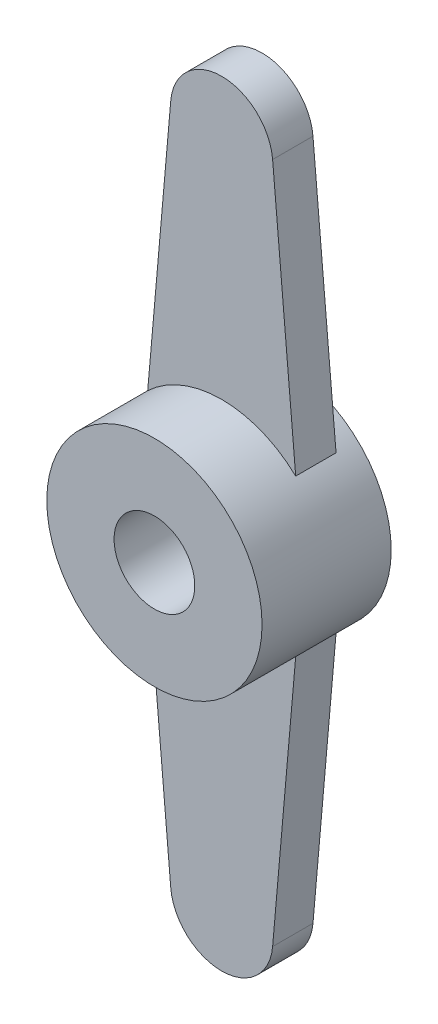
SolidWorks part; units mm, degrees
ref_plane "Front Plane" through (0, 0, 0) normal (0, 0, 1) x (1, 0, 0)
ref_plane "Top Plane" through (0, 0, 0) normal (0, 1, 0) x (1, 0, 0)
ref_plane "Right Plane" through (0, 0, 0) normal (1, 0, 0) x (0, 0, -1)
sketch "Sketch1" plane through (0, 0, 0) normal (0, 0, 1) x (1, 0, 0)
  line L0 (0, 0) -> (0, 15282.2833) construction
  line L1 (0, 0) -> (15282.2833, 0) construction
  line L2 (-1.8927, 12.6662) -> (-2.75, 2.9047)
  line L3 (1.8927, 12.6662) -> (2.75, 2.9047)
  line L4 (-2.75, -2.9047) -> (-1.8927, -12.6662)
  line L5 (2.75, -2.9047) -> (1.8927, -12.6662)
  line L6 (-2.75, -2.9047) -> (2.75, -2.9047) construction
  line L7 (2.75, 2.9047) -> (-2.75, 2.9047) construction
  line L8 (-2.75, 2.9047) -> (-2.75, -2.9047) construction
  line L9 (2.75, 2.9047) -> (2.75, -2.9047) construction
  arc A0 (2.75, -2.9047) -> (2.75, 2.9047) centre (0, 0) ccw
  arc A1 (1.8927, 12.6662) -> (-1.8927, 12.6662) centre (0, 12.5) ccw
  arc A2 (-1.8927, -12.6662) -> (1.8927, -12.6662) centre (0, -12.5) ccw
  arc A3 (-2.75, 2.9047) -> (-2.75, -2.9047) centre (0, 0) ccw
  dimension "D2" = 3.8
  dimension "D3" = 8
  dimension "D1" = 25
  dimension "D4" = 5.5
extrude "Boss-Extrude1" add sketch "Sketch1" along normal blind 1.5
sketch "Sketch2" plane through (0, 0, 1.5) normal (0, 0, 1) x (1, 0, 0)
  circle A0 centre (0, 0) radius 4
extrude "Boss-Extrude2" add sketch "Sketch2" along normal blind 2.5
sketch "Sketch3" plane through (0, 0, 0) normal (0, 0, -1) x (-1, 0, 0)
  circle A0 centre (0, 0) radius 4
extrude "Boss-Extrude3" add sketch "Sketch3" along normal blind 0.8
sketch "Sketch4" plane through (0, 0, -0.8) normal (0, 0, -1) x (-1, 0, 0)
  circle A0 centre (0, 0) radius 1.5
  dimension "D1" = 3
extrude "Cut-Extrude1" cut sketch "Sketch4" against normal through all
